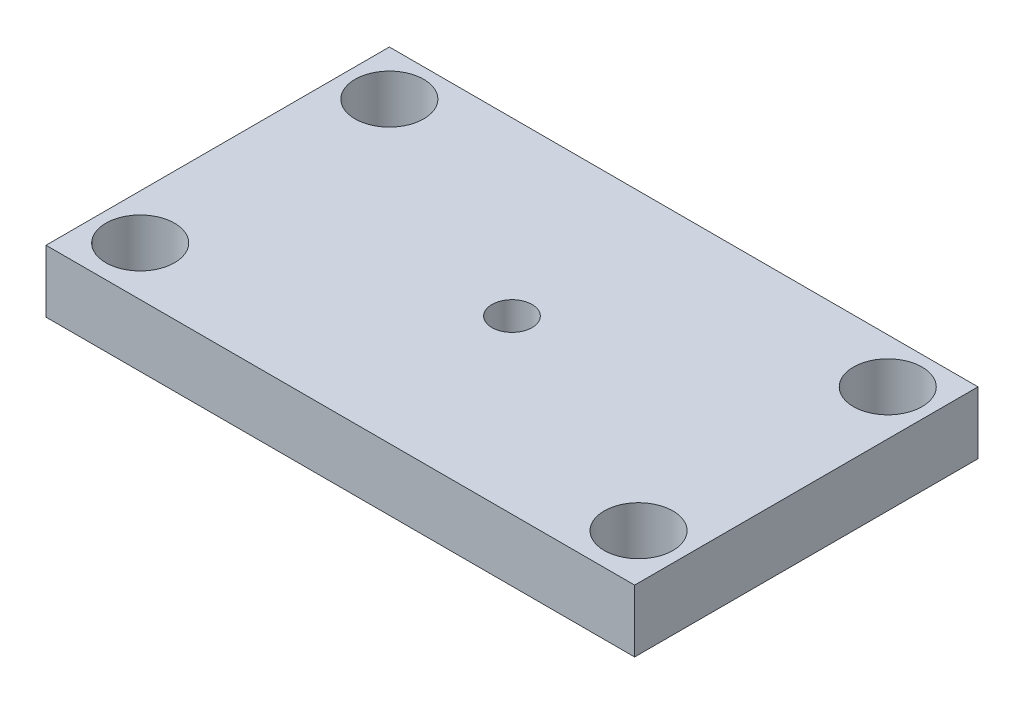
SolidWorks part; units mm, degrees
ref_plane "Front Plane" through (0, 0, 0) normal (0, 0, 1) x (1, 0, 0)
ref_plane "Top Plane" through (0, 0, 0) normal (0, 1, 0) x (1, 0, 0)
ref_plane "Right Plane" through (0, 0, 0) normal (1, 0, 0) x (0, 0, -1)
sketch "Sketch1" plane through (0, 0, 0) normal (0, 1, 0) x (1, 0, 0)
  line L0 (4.6, 30.4) -> (0, 30.4) construction
  line L1 (0, 0) -> (60, 0)
  line L2 (0, 0) -> (0, 35)
  line L3 (0, 35) -> (60, 35)
  line L4 (60, 0) -> (60, 35)
  line L5 (4.6, 30.4) -> (55.4, 30.4) construction
  line L6 (4.6, 30.4) -> (4.6, 5) construction
  line L7 (4.6, 5) -> (55.4, 5) construction
  line L8 (55.4, 30.4) -> (55.4, 5) construction
  line L9 (4.6, 30.4) -> (4.6, 35) construction
  circle A0 centre (4.6, 30.4) radius 3.5
  circle A1 centre (55.4, 30.4) radius 3.5
  circle A2 centre (4.6, 5) radius 3.5
  circle A3 centre (55.4, 5) radius 3.5
  circle A4 centre (30, 17.5) radius 2.0447
  point P13 (30, 30.4)
  point P14 (30, 35)
  point P20 (60, 17.5)
  dimension "D5" = 7
  dimension "D6" = 4.0894
  dimension "D1" = 60
  dimension "D2" = 35
  dimension "D3" = 50.8
  dimension "D4" = 25.4
extrude "Boss-Extrude1" add sketch "Sketch1" along normal blind 6.35
